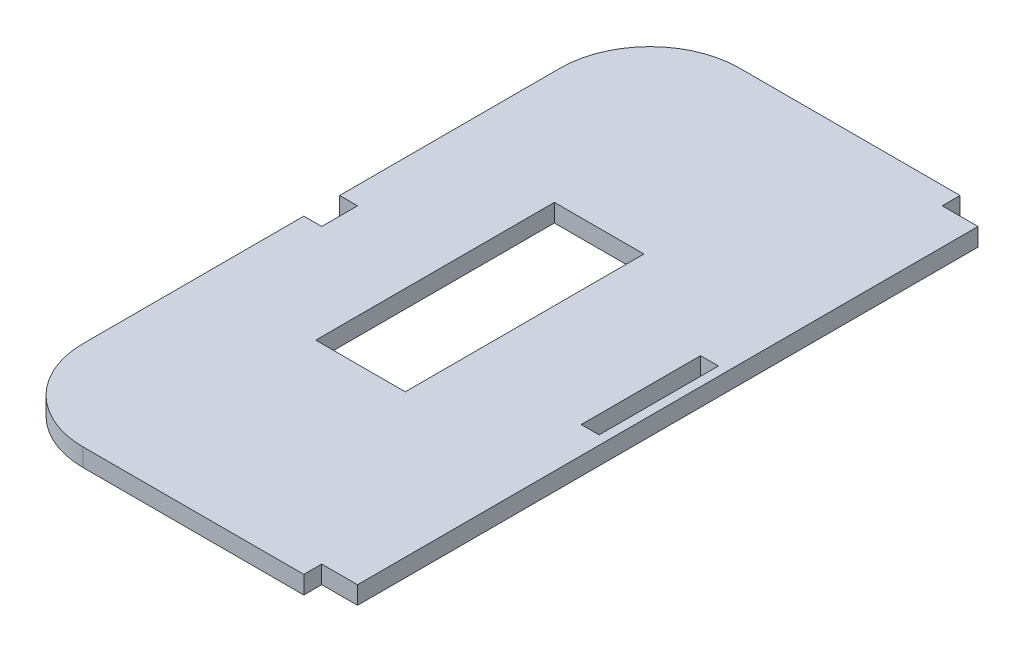
SolidWorks part; units mm, degrees
ref_plane "Спереди" through (0, 0, 0) normal (0, 0, 1) x (1, 0, 0)
ref_plane "Сверху" through (0, 0, 0) normal (0, 1, 0) x (1, 0, 0)
ref_plane "Справа" through (0, 0, 0) normal (1, 0, 0) x (0, 0, -1)
other "Configuration Table"
sketch "Эскиз4" plane through (0, 0, 0) normal (0, 1, 0) x (1, 0, 0)
  line L1 (0, 0) -> (52, 0)
  line L2 (0, 0) -> (0, 52)
  line L3 (0, 110) -> (52, 110)
  line L6 (55, 107) -> (52, 107)
  line L7 (52, 107) -> (55, 107)
  line L8 (55, 107) -> (58, 107)
  line L9 (52, 107) -> (52, 110)
  line L12 (55, 3) -> (58, 3)
  line L13 (55, 3) -> (52, 3)
  line L14 (52, 3) -> (52, 0)
  line L15 (3, 55) -> (3, 58)
  line L16 (3, 55) -> (3, 52)
  line L17 (3, 58) -> (0, 58)
  line L18 (3, 52) -> (0, 52)
  line L19 (55, 107) -> (55, 3) construction
  line L20 (3, 55) -> (55, 55) construction
  line L21 (58, 107) -> (58, 3)
  line L22 (0, 58) -> (0, 110)
  dimension "D1" = 55
  dimension "D2" = 110
  dimension "D3" = 3
  dimension "D4" = 3
  dimension "D5" = 6
  dimension "D6" = 3
  dimension "D7" = 3
  dimension "D8" = 3
  dimension "D10" = 3
  dimension "D12" = 3
extrude "Бобышка-Вытянуть3" add sketch "Эскиз4" along normal blind 3 contours L3 L8 L6 L9 L2 L17 L15 L16 L18 L1 L14 L13 L12 region at (28.9303, 0, -55)
sketch "Sketch1" plane through (0, 3, 0) normal (0, 1, 0) x (1, 0, 0)
  line L0 (3, 52) -> (3, 58) construction
  line L13 (3, 55) -> (107, 55) construction
  line L15 (55, 107) -> (55, 3) construction
  line L16 (52, 107) -> (58, 107) construction
  line L19 (19, 75) -> (34, 75)
  line L20 (19, 75) -> (19, 35)
  line L21 (19, 35) -> (34, 35)
  line L22 (34, 75) -> (34, 35)
  line L23 (53.5, 65) -> (56.5, 65)
  line L24 (53.5, 65) -> (53.5, 45)
  line L25 (53.5, 45) -> (56.5, 45)
  line L26 (56.5, 65) -> (56.5, 45)
  dimension "D1" = 3
  dimension "D2" = 20
  dimension "D3" = 16
  dimension "D4" = 15
  dimension "D5" = 40
extrude "Cut-Extrude1" cut sketch "Sketch1" against normal blind 10
fillet "Fillet1" radius 15 2 edges at (0, 1.5, 0) (0, 1.5, -110)
